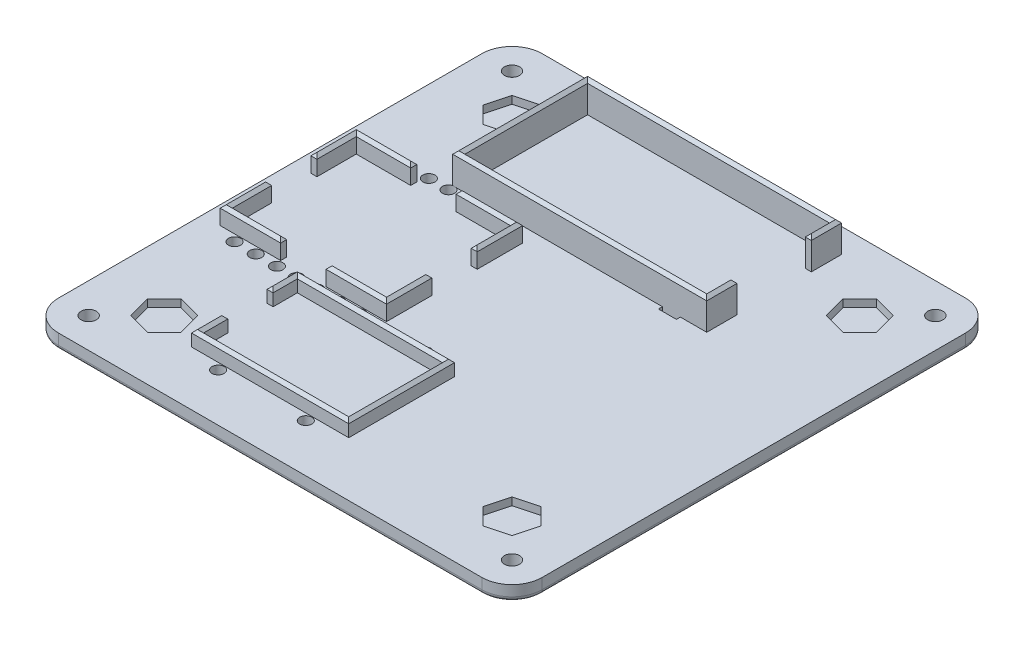
SolidWorks part; units mm, degrees
ref_plane "Front Plane" through (0, 0, 0) normal (0, 0, 1) x (1, 0, 0)
ref_plane "Top Plane" through (0, 0, 0) normal (0, 1, 0) x (1, 0, 0)
ref_plane "Right Plane" through (0, 0, 0) normal (1, 0, 0) x (0, 0, -1)
sketch "Sketch1" plane through (0, 0, 0) normal (0, 1, 0) x (1, 0, 0)
  line L1 (0, 0) -> (203.2, 0)
  line L2 (0, 0) -> (0, 203.2)
  line L3 (0, 203.2) -> (203.2, 203.2)
  line L4 (203.2, 0) -> (203.2, 203.2)
  dimension "D1" = 203.2
  dimension "D2" = 203.2
extrude "Boss-Extrude1" add sketch "Sketch1" along normal blind 6.35
fillet "Fillet1" radius 12.7 4 edges at (0, 3.175, -203.2) (0, 3.175, 0) (203.2, 3.175, 0) (203.2, 3.175, -203.2)
sketch "Sketch2" plane through (0, 0, 0) normal (0, -1, 0) x (1, 0, 0)
  circle A0 centre (12.7, -12.7) radius 3.175
  circle A1 centre (190.5, -12.7) radius 3.175
  circle A2 centre (190.5, -190.5) radius 3.175
  circle A3 centre (12.7, -190.5) radius 3.175
  arc A4 (190.5, -203.2) -> (203.2, -190.5) centre (190.5, -190.5) ccw construction
  arc A5 (12.7, 0) -> (0, -12.7) centre (12.7, -12.7) ccw construction
  dimension "D1" = 6.35
extrude "Cut-Extrude1" cut sketch "Sketch2" against normal through all
sketch "Sketch22" plane through (0, 6.35, 0) normal (0, 1, 0) x (1, 0, 0)
  line L17 (190.5, 203.2) -> (12.7, 203.2) construction
  line L18 (203.2, 12.7) -> (203.2, 190.5) construction
  line L21 (181.6542, 181.6542) -> (172.0521, 184.2271)
  line L22 (172.0521, 184.2271) -> (165.0229, 177.1979)
  line L23 (165.0229, 177.1979) -> (167.5958, 167.5958)
  line L24 (167.5958, 167.5958) -> (177.1979, 165.0229)
  line L25 (177.1979, 165.0229) -> (184.2271, 172.0521)
  line L26 (184.2271, 172.0521) -> (181.6542, 181.6542)
  line L27 (174.625, 174.625) -> (190.5, 190.5) construction
  line L28 (101.6, 203.2) -> (101.6, 0) construction
  line L29 (12.7, 0) -> (190.5, 0) construction
  line L30 (203.2, 101.6) -> (0, 101.6) construction
  line L31 (0, 190.5) -> (0, 12.7) construction
  line L32 (28.575, 174.625) -> (12.7, 190.5) construction
  line L33 (18.9729, 172.0521) -> (21.5458, 181.6542)
  line L34 (26.0021, 165.0229) -> (18.9729, 172.0521)
  line L35 (35.6042, 167.5958) -> (26.0021, 165.0229)
  line L36 (38.1771, 177.1979) -> (35.6042, 167.5958)
  line L37 (31.1479, 184.2271) -> (38.1771, 177.1979)
  line L38 (21.5458, 181.6542) -> (31.1479, 184.2271)
  line L39 (174.625, 28.575) -> (190.5, 12.7) construction
  line L40 (184.2271, 31.1479) -> (181.6542, 21.5458)
  line L41 (177.1979, 38.1771) -> (184.2271, 31.1479)
  line L42 (167.5958, 35.6042) -> (177.1979, 38.1771)
  line L43 (165.0229, 26.0021) -> (167.5958, 35.6042)
  line L44 (172.0521, 18.9729) -> (165.0229, 26.0021)
  line L45 (181.6542, 21.5458) -> (172.0521, 18.9729)
  line L46 (28.575, 28.575) -> (12.7, 12.7) construction
  line L47 (21.5458, 21.5458) -> (31.1479, 18.9729)
  line L48 (31.1479, 18.9729) -> (38.1771, 26.0021)
  line L49 (38.1771, 26.0021) -> (35.6042, 35.6042)
  line L50 (35.6042, 35.6042) -> (26.0021, 38.1771)
  line L51 (26.0021, 38.1771) -> (18.9729, 31.1479)
  line L52 (18.9729, 31.1479) -> (21.5458, 21.5458)
  circle A0 centre (174.625, 174.625) radius 8.609 construction
  circle A1 centre (28.575, 174.625) radius 8.609 construction
  circle A2 centre (174.625, 28.575) radius 8.609 construction
  circle A3 centre (28.575, 28.575) radius 8.609 construction
  dimension "D5" = 17.218
  dimension "D3" = 28.575
  dimension "D4" = 28.575
extrude "Cut-Extrude2" cut sketch "Sketch22" against normal blind 3.175
sketch "Sketch23" plane through (0, 6.35, 0) normal (0, 1, 0) x (1, 0, 0)
  line L0 (0, 190.5) -> (0, 12.7) construction
  line L1 (77.47, 130.175) -> (52.07, 130.175)
  line L2 (77.47, 130.175) -> (77.47, 111.125)
  line L3 (77.47, 73.025) -> (52.07, 73.025)
  line L4 (7.62, 130.175) -> (7.62, 111.125)
  line L5 (7.62, 130.175) -> (7.62, 203.2) construction
  line L6 (190.5, 203.2) -> (12.7, 203.2) construction
  line L7 (7.62, 73.025) -> (7.62, 0) construction
  line L8 (12.7, 0) -> (190.5, 0) construction
  line L9 (33.02, 130.175) -> (33.02, 127.635)
  line L10 (74.93, 127.635) -> (52.07, 127.635)
  line L11 (74.93, 127.635) -> (74.93, 111.125)
  line L12 (74.93, 75.565) -> (52.07, 75.565)
  line L13 (10.16, 127.635) -> (10.16, 111.125)
  line L14 (52.07, 130.175) -> (52.07, 127.635)
  line L15 (77.47, 111.125) -> (74.93, 111.125)
  line L16 (77.47, 92.075) -> (74.93, 92.075)
  line L17 (10.16, 111.125) -> (7.62, 111.125)
  line L18 (10.16, 92.075) -> (7.62, 92.075)
  line L19 (33.02, 75.565) -> (33.02, 73.025)
  line L20 (52.07, 75.565) -> (52.07, 73.025)
  line L21 (33.02, 130.175) -> (7.62, 130.175)
  line L22 (33.02, 127.635) -> (10.16, 127.635)
  line L23 (77.47, 92.075) -> (77.47, 73.025)
  line L24 (74.93, 92.075) -> (74.93, 75.565)
  line L25 (33.02, 75.565) -> (10.16, 75.565)
  line L26 (33.02, 73.025) -> (7.62, 73.025)
  line L27 (10.16, 92.075) -> (10.16, 75.565)
  line L28 (7.62, 92.075) -> (7.62, 73.025)
  point P32 (33.02, 128.905)
  dimension "D1" = 7.62
  dimension "D2" = 57.15
  dimension "D3" = 69.85
  dimension "D4" = 2.54
  dimension "D5" = 2.54
  dimension "D6" = 2.54
  dimension "D7" = 2.54
  dimension "D8" = 19.05
  dimension "D9" = 19.05
  dimension "D10" = 25.4
  dimension "D11" = 25.4
  dimension "D12" = 19.05
  dimension "D13" = 19.05
  dimension "D14" = 25.4
  dimension "D15" = 25.4
extrude "Boss-Extrude2" add sketch "Sketch23" along normal blind 7.62
chamfer "Chamfer1" distance 1.27 angle 45 24 edges at (8.89, 13.97, -92.075) (10.16, 13.97, -83.82) (21.59, 13.97, -75.565) (33.02, 13.97, -74.295) (20.32, 13.97, -73.025) (7.62, 13.97, -82.55) (64.77, 13.97, -73.025) (52.07, 13.97, -74.295) (63.5, 13.97, -75.565) (74.93, 13.97, -83.82) (76.2, 13.97, -92.075) (77.47, 13.97, -82.55) (76.2, 13.97, -111.125) (74.93, 13.97, -119.38) (63.5, 13.97, -127.635) (52.07, 13.97, -128.905) (64.77, 13.97, -130.175) (77.47, 13.97, -120.65) (33.02, 13.97, -128.905) (21.59, 13.97, -127.635) (10.16, 13.97, -119.38) (8.89, 13.97, -111.125) (7.62, 13.97, -120.65) (20.32, 13.97, -130.175)
sketch "Sketch24" plane through (0, 6.35, 0) normal (0, 1, 0) x (1, 0, 0)
  line L0 (12.7, 0) -> (190.5, 0) construction
  line L1 (109.22, 64.77) -> (48.26, 64.77)
  line L2 (109.22, 64.77) -> (109.22, 25.4)
  line L3 (109.22, 25.4) -> (48.26, 25.4)
  line L4 (48.26, 64.77) -> (48.26, 54.61)
  line L5 (0, 190.5) -> (0, 12.7) construction
  line L6 (111.76, 67.31) -> (45.72, 67.31)
  line L7 (111.76, 67.31) -> (111.76, 22.86)
  line L8 (111.76, 22.86) -> (45.72, 22.86)
  line L9 (45.72, 67.31) -> (45.72, 54.61)
  line L10 (45.72, 54.61) -> (48.26, 54.61)
  line L11 (45.72, 35.56) -> (48.26, 35.56)
  line L12 (45.72, 35.56) -> (45.72, 22.86)
  line L13 (48.26, 35.56) -> (48.26, 25.4)
  dimension "D1" = 39.37
  dimension "D2" = 60.96
  dimension "D3" = 25.4
  dimension "D4" = 2.54
  dimension "D5" = 2.54
  dimension "D6" = 2.54
  dimension "D7" = 2.54
  dimension "D8" = 48.26
  dimension "D9" = 12.7
  dimension "D10" = 12.7
extrude "Boss-Extrude3" add sketch "Sketch24" along normal blind 6.35
chamfer "Chamfer2" distance 1.27 angle 45 12 edges at (78.74, 12.7, -64.77) (48.26, 12.7, -59.69) (46.99, 12.7, -54.61) (45.72, 12.7, -60.96) (78.74, 12.7, -67.31) (111.76, 12.7, -45.085) (78.74, 12.7, -22.86) (45.72, 12.7, -29.21) (46.99, 12.7, -35.56) (48.26, 12.7, -30.48) (78.74, 12.7, -25.4) (109.22, 12.7, -45.085)
sketch "Sketch25" plane through (0, 6.35, 0) normal (0, 1, 0) x (1, 0, 0)
  line L0 (74.93, 127.635) -> (74.93, 111.125) construction
  line L1 (10.16, 111.125) -> (10.16, 127.635) construction
  line L2 (34.29, 133.985) -> (42.545, 133.985) construction
  line L3 (42.545, 133.985) -> (50.8, 133.985) construction
  line L4 (33.02, 130.175) -> (7.62, 130.175) construction
  line L5 (10.16, 75.565) -> (10.16, 92.075) construction
  line L6 (74.93, 92.075) -> (74.93, 75.565) construction
  line L7 (34.29, 70.1675) -> (42.545, 70.1675) construction
  line L8 (42.545, 70.1675) -> (50.8, 70.1675) construction
  line L9 (68.58, 70.1675) -> (68.58, 73.025) construction
  line L10 (52.07, 73.025) -> (77.47, 73.025) construction
  line L11 (68.58, 70.1675) -> (68.58, 67.31) construction
  line L12 (111.76, 67.31) -> (45.72, 67.31) construction
  line L13 (109.22, 64.77) -> (109.22, 25.4) construction
  line L14 (45.72, 22.86) -> (111.76, 22.86) construction
  circle A0 centre (68.58, 70.1675) radius 2.54
  circle A1 centre (59.69, 70.1675) radius 2.54
  circle A2 centre (50.8, 70.1675) radius 2.54
  circle A3 centre (42.545, 70.1675) radius 2.54
  circle A4 centre (34.29, 70.1675) radius 2.54
  circle A5 centre (25.4, 70.1675) radius 2.54
  circle A6 centre (16.51, 70.1675) radius 2.54
  circle A7 centre (16.51, 133.985) radius 2.54
  circle A8 centre (25.4, 133.985) radius 2.54
  circle A9 centre (34.29, 133.985) radius 2.54
  circle A10 centre (42.545, 133.985) radius 2.54
  circle A11 centre (50.8, 133.985) radius 2.54
  circle A12 centre (59.69, 133.985) radius 2.54
  circle A13 centre (68.58, 133.985) radius 2.54
  circle A16 centre (96.52, 70.104) radius 2.54
  circle A18 centre (96.52, 20.066) radius 2.54
  circle A19 centre (59.69, 20.066) radius 2.54
  dimension "D1" = 5.08
  dimension "D2" = 6.35
  dimension "D3" = 8.89
  dimension "D4" = 8.89
  dimension "D5" = 6.35
  dimension "D6" = 8.89
  dimension "D7" = 8.89
  dimension "D8" = 3.81
  dimension "D9" = 6.35
  dimension "D10" = 8.89
  dimension "D11" = 8.89
  dimension "D12" = 6.35
  dimension "D13" = 8.89
  dimension "D14" = 8.89
  dimension "D15" = 12.7
  dimension "D16" = 12.7
  dimension "D17" = 2.794
  dimension "D18" = 2.794
  dimension "D19" = 2.794
  dimension "D20" = 36.83
extrude "Cut-Extrude3" cut sketch "Sketch25" against normal blind 6.35
sketch "Sketch26" plane through (0, 6.35, 0) normal (0, 1, 0) x (1, 0, 0)
  line L0 (190.5, 203.2) -> (12.7, 203.2) construction
  line L1 (146.05, 190.5) -> (44.45, 190.5)
  line L2 (146.05, 190.5) -> (146.05, 180.34)
  line L3 (146.05, 138.938) -> (44.45, 138.938)
  line L4 (44.45, 190.5) -> (44.45, 138.938)
  line L5 (0, 190.5) -> (0, 12.7) construction
  line L6 (148.59, 180.34) -> (146.05, 180.34)
  line L7 (41.91, 136.398) -> (148.59, 136.398)
  line L8 (41.91, 136.398) -> (41.91, 193.04)
  line L9 (41.91, 193.04) -> (148.59, 193.04)
  line L10 (148.59, 136.398) -> (148.59, 149.098)
  line L11 (148.59, 149.098) -> (146.05, 149.098)
  line L12 (148.59, 180.34) -> (148.59, 193.04)
  line L13 (146.05, 149.098) -> (146.05, 138.938)
  dimension "D1" = 101.6
  dimension "D2" = 51.562
  dimension "D3" = 12.7
  dimension "D4" = 44.45
  dimension "D5" = 2.54
  dimension "D6" = 2.54
  dimension "D7" = 2.54
  dimension "D8" = 2.54
  dimension "D9" = 12.7
  dimension "D10" = 12.7
extrude "Boss-Extrude4" add sketch "Sketch26" along normal blind 12.7
chamfer "Chamfer3" distance 1.27 angle 45 12 edges at (95.25, 19.05, -190.5) (44.45, 19.05, -164.719) (95.25, 19.05, -138.938) (146.05, 19.05, -144.018) (147.32, 19.05, -149.098) (148.59, 19.05, -142.748) (95.25, 19.05, -136.398) (41.91, 19.05, -164.719) (95.25, 19.05, -193.04) (148.59, 19.05, -186.69) (147.32, 19.05, -180.34) (146.05, 19.05, -185.42)
sketch "Sketch27" plane through (0, 6.35, 0) normal (0, 1, 0) x (1, 0, 0)
  line L0 (148.59, 193.04) -> (41.91, 193.04) construction
  line L1 (137.5111, 193.04) -> (129.9648, 193.04)
  line L2 (137.5111, 193.04) -> (137.5111, 195.5891)
  line L3 (137.5111, 195.5891) -> (129.9648, 195.5891)
  line L4 (129.9648, 193.04) -> (129.9648, 195.5891)
  line L5 (69.3731, 136.398) -> (148.59, 136.398) construction
  line L6 (61.4746, 193.04) -> (54.0114, 193.04)
  line L7 (61.4746, 193.04) -> (61.4746, 195.5891)
  line L8 (61.4746, 195.5891) -> (54.0114, 195.5891)
  line L9 (54.0114, 193.04) -> (54.0114, 195.5891)
  line L10 (137.5111, 136.398) -> (129.9648, 136.398)
  line L11 (137.5111, 136.398) -> (137.5111, 134.7213)
  line L12 (137.5111, 134.7213) -> (129.9648, 134.7213)
  line L13 (129.9648, 136.398) -> (129.9648, 134.7213)
extrude "Cut-Extrude4" cut sketch "Sketch27" against normal blind 12.7
fillet "Fillet2" radius 1.905 41 edges at (3.7197, 0, -3.7197) (101.6, 0, 0) (199.4803, 0, -3.7197) (203.2, 0, -101.6) (199.4803, 0, -199.4803) (101.6, 0, -203.2) (3.7197, 0, -199.4803) (0, 0, -101.6) (12.7, 0, -15.875) (190.5, 0, -15.875) (190.5, 0, -193.675) (12.7, 0, -193.675) (68.58, 0, -67.6275) (34.29, 0, -131.445) (42.545, 0, -131.445) (50.8, 0, -131.445) (59.69, 0, -131.445) (96.52, 0, -67.564) (59.69, 0, -17.526) (96.52, 0, -17.526) (68.58, 0, -131.445) (25.4, 0, -131.445) (16.51, 0, -131.445) (16.51, 0, -67.6275) (25.4, 0, -67.6275) (34.29, 0, -67.6275) (42.545, 0, -67.6275) (50.8, 0, -67.6275) (59.69, 0, -67.6275) (133.7379, 0, -193.04) (129.9648, 0, -194.3146) (133.7379, 0, -195.5891) (137.5111, 0, -194.3146) (57.743, 0, -193.04) (54.0114, 0, -194.3146) (57.743, 0, -195.5891) (61.4746, 0, -194.3146) (133.7379, 0, -134.7213) (129.9648, 0, -135.5596) (133.7379, 0, -136.398) (137.5111, 0, -135.5596)
